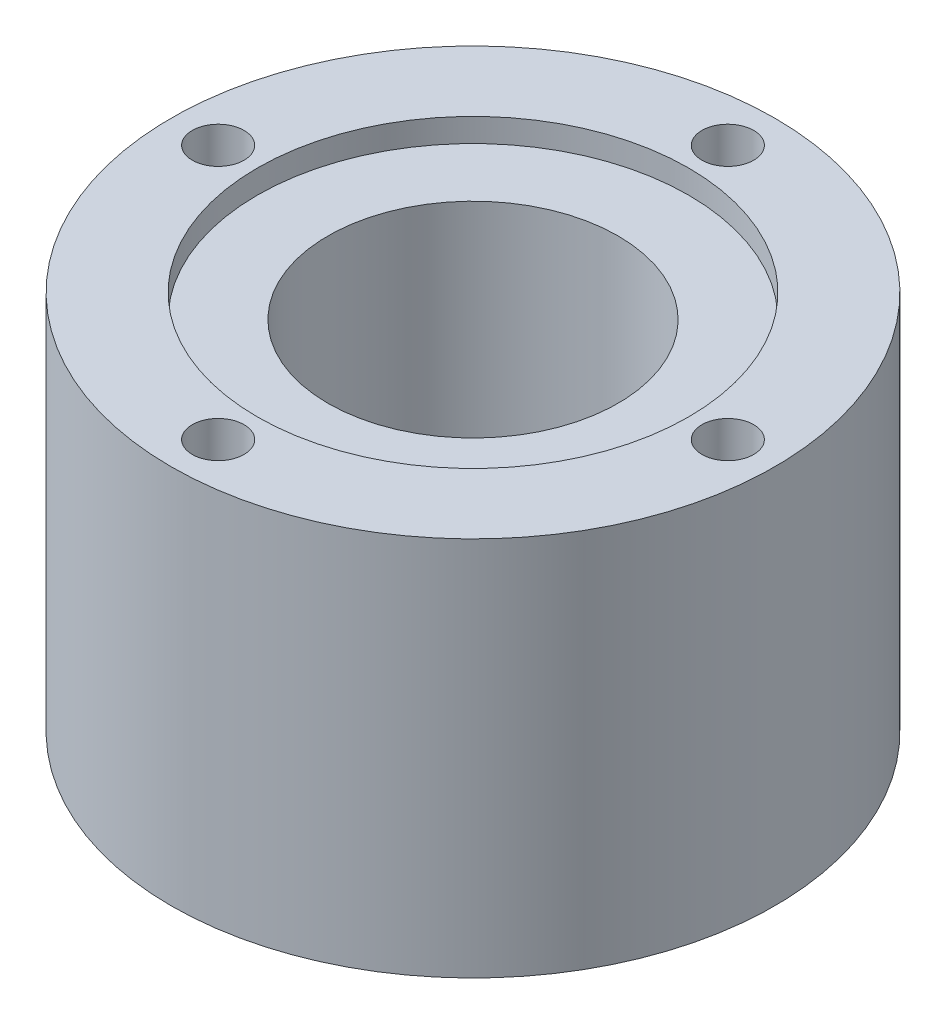
SolidWorks part; units mm, degrees
material "PA38 (3.3206)"
ref_plane "Płaszczyzna przednia" through (0, 0, 0) normal (0, 0, 1) x (1, 0, 0)
ref_plane "Płaszczyzna górna" through (0, 0, 0) normal (0, 1, 0) x (1, 0, 0)
ref_plane "Płaszczyzna prawa" through (0, 0, 0) normal (1, 0, 0) x (0, 0, -1)
sketch "Szkic1" plane through (0, 0, 0) normal (1, 0, 0) x (0, 0, -1)
  line L0 (0, 14) -> (0, -14) construction
  line L1 (-23.5, -14) -> (-38.5, -14)
  line L2 (-38.5, -14) -> (-38.5, 34.5)
  line L3 (-23.5, -14) -> (-23.5, 0)
  line L4 (-23.5, 0) -> (-18.5, 0)
  line L5 (-18.5, 0) -> (-18.5, 34.5)
  line L6 (-18.5, 34.5) -> (-38.5, 34.5)
  dimension "D1" = 47
  dimension "D2" = 37
  dimension "D3" = 14
  dimension "D4" = 77
  dimension "D5" = 48.5
revolve "Obrót1" add sketch "Szkic1" angle 360 about L0
hole_wizard "Otwór pod śrubę M61" positions "Szkic2" profile "Szkic3" hole size "M6" standard "DIN" end condition up to next
sketch "Szkic2" plane through (0, 34.5, 0) normal (0, 1, 0) x (1, 0, 0)
  line L0 (0, 0) -> (0, 32.5) construction
  point P0 (0, 32.5)
  dimension "D1" = 32.5
sketch "Szkic3" plane through (0, 34.5, -32.5) normal (1, 0, 0) x (0, 0, 1)
  line L0 (0, 0) -> (0, 48.501)
  line L1 (0, 48.501) -> (3.3, 48.501)
  line L2 (3.3, 48.501) -> (3.3, 0)
  line L5 (3.3, 0) -> (0, 0)
  line L11 (0, -6.35) -> (0, 107.95) construction
  dimension "Średnica otworu na wylot" = 6.6
  dimension "Głębokość otworu na wylot" = 48.501
pattern_circular "Szyk kołowy1" count 4 over 360 about axis through (0, 14, 0) along (0, 1, 0) of "Otwór pod śrubę M61" reverse direction yes
sketch "Szkic4" plane through (0, 34.5, 0) normal (0, 1, 0) x (1, 0, 0)
  circle A0 centre (0, 0) radius 27.5
  dimension "D1" = 55
extrude "Wytnij-wyciągnięcie1" cut sketch "Szkic4" against normal blind 3
